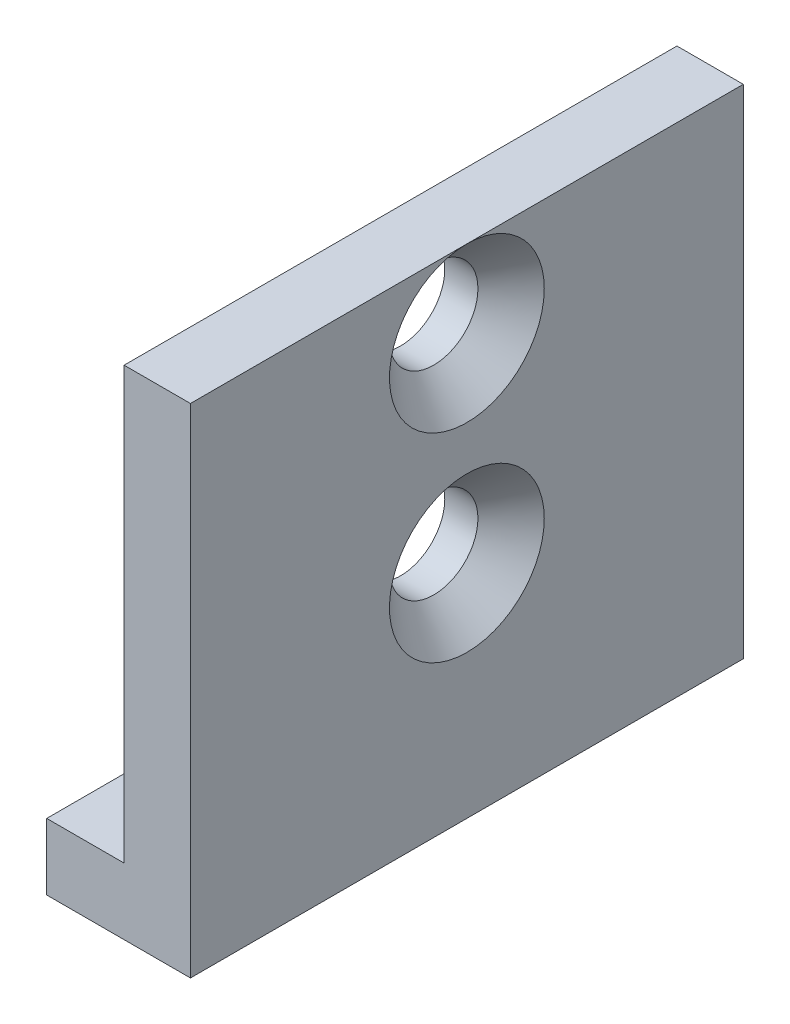
SolidWorks part; units mm, degrees
material "Brass"
ref_plane "Front Plane" through (0, 0, 0) normal (0, 0, 1) x (1, 0, 0)
ref_plane "Top Plane" through (0, 0, 0) normal (0, 1, 0) x (1, 0, 0)
ref_plane "Right Plane" through (0, 0, 0) normal (1, 0, 0) x (0, 0, -1)
sketch "Sketch1" plane through (0, 0, 0) normal (0, 0, 1) x (1, 0, 0)
  line L0 (-59.3656, 18.3861) -> (-59.3656, 63.3861)
  line L1 (-59.3656, 63.3861) -> (-65.3656, 63.3861)
  line L2 (-65.3656, 63.3861) -> (-65.3656, 24.3861)
  line L6 (-65.3656, 24.3861) -> (-72.3656, 24.3861)
  line L7 (-72.3656, 24.3861) -> (-72.3656, 18.3861)
  line L8 (-72.3656, 18.3861) -> (-59.3656, 18.3861)
  line L9 (-65.3656, 24.3861) -> (-72.3656, 24.3861) construction
  line L10 (-72.3656, 24.3861) -> (-72.3656, 18.3861) construction
  line L11 (-72.3656, 18.3861) -> (-65.3656, 18.3861) construction
  line L12 (-65.3656, 37.3861) -> (-65.3656, 24.3861) construction
  dimension "D1" = 45
  dimension "D3" = 6
extrude "Boss-Extrude1" add sketch "Sketch1" along normal mid plane 50
hole_wizard "Ø1.0mm Dowel Hole1" positions "Sketch2" profile "Sketch3" hole size "Ø1.0" standard "ANSI Metric" end condition up to next
sketch "Sketch2" plane through (-59.3656, 0, 0) normal (1, 0, 0) x (0, 0, -1)
  line L0 (-25, 63.3861) -> (25, 63.3861) construction
  point P0 (0, 56.3861)
  point P2 (0, 38.3861)
  dimension "D1" = 7
  dimension "D2" = 18
sketch "Sketch3" plane through (-59.3656, 56.3861, 0) normal (0, 1, 0) x (0, 0, -1)
  line L0 (0, 0) -> (0, 6)
  line L1 (0, 6) -> (4, 6)
  line L2 (4, 6) -> (4, 0)
  line L5 (4, 0) -> (0, 0)
  line L11 (0, -6.35) -> (0, 107.95) construction
  dimension "Thru Hole Dia." = 8
  dimension "Thru Hole Depth" = 6
chamfer "Chamfer1" distance 3 angle 45 2 edges at (-59.3656, 56.3861, -4) (-59.3656, 38.3861, -4)
